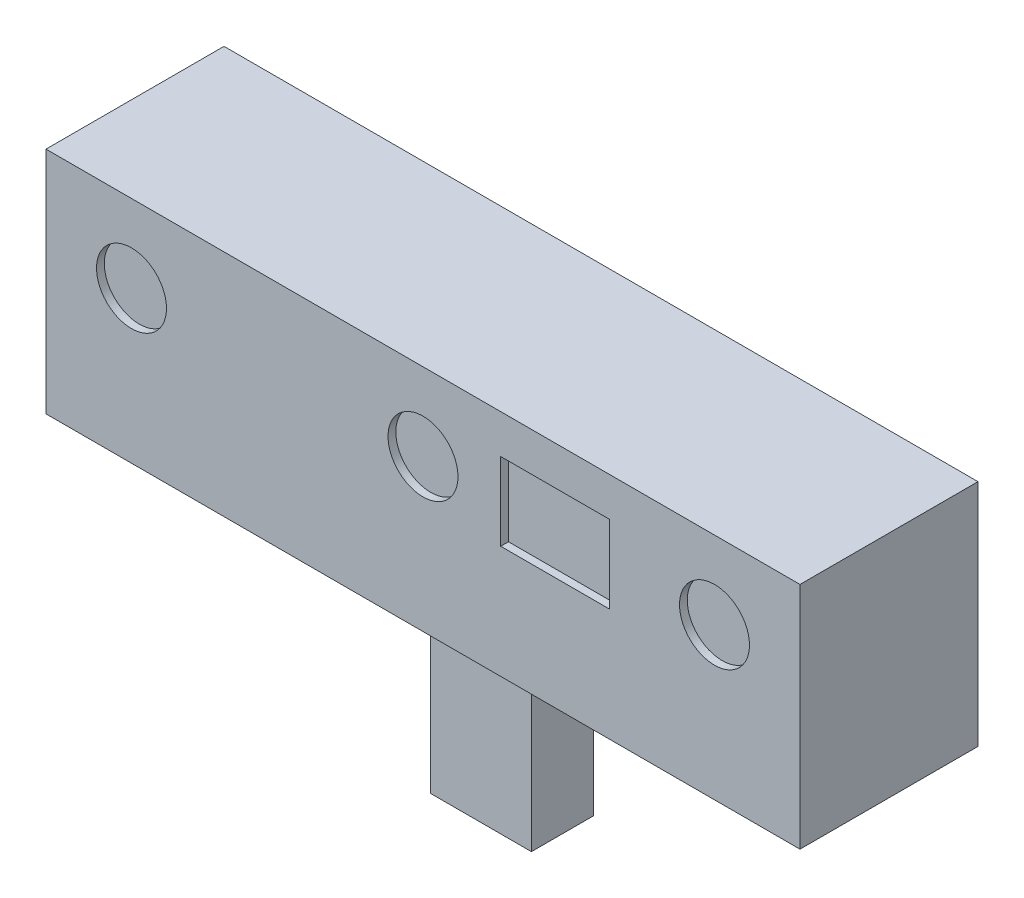
SolidWorks part; units mm, degrees
ref_plane "Front Plane" through (0, 0, 0) normal (0, 0, 1) x (1, 0, 0)
ref_plane "Top Plane" through (0, 0, 0) normal (0, 1, 0) x (1, 0, 0)
ref_plane "Right Plane" through (0, 0, 0) normal (1, 0, 0) x (0, 0, -1)
sketch "SK_Body" plane through (0, 0, 0) normal (0, 0, 1) x (1, 0, 0)
  line L1 (-48.5, -19.5) -> (48.5, -19.5)
  line L2 (-48.5, -19.5) -> (-48.5, 10)
  line L3 (-48.5, 10) -> (48.5, 10)
  line L4 (48.5, -19.5) -> (48.5, 10)
  dimension "D1" = 97
  dimension "D2" = 29.5
  dimension "D3" = 48.5
  dimension "D4" = 19.5
extrude "EX_Body" add sketch "SK_Body" along normal blind 22.9
sketch "SK_VESA_2xM4" plane through (0, 0, 0) normal (0, 0, 1) x (1, 0, 0)
  circle A0 centre (37.5, -4.75) radius 1.65
  circle A1 centre (-37.5, -4.75) radius 1.65
  dimension "D3" = 3.3
  dimension "D6" = 3.3
  dimension "D1" = 37.5
  dimension "D2" = 4.75
  dimension "D4" = 37.5
  dimension "D5" = 4.75
extrude "CUT_VESA_2xM4" cut sketch "SK_VESA_2xM4" along normal blind 8
ref_plane "PL_Xp22_9" through (0, 0, 22.9) normal (0, 0, 1) x (1, 0, 0)
sketch "SK_Lenses" plane through (0, 0, 22.9) normal (0, 0, 1) x (1, 0, 0)
  line L1 (10, -5) -> (24, -5)
  line L2 (10, -5) -> (10, 5)
  line L3 (10, 5) -> (24, 5)
  line L4 (24, -5) -> (24, 5)
  circle A0 centre (37.5, 0) radius 4.5
  circle A1 centre (-37.5, 0) radius 4.5
  circle A2 centre (0, 0) radius 4.5
  dimension "D2" = 9
  dimension "D4" = 9
  dimension "D5" = 9
  dimension "D1" = 37.5
  dimension "D3" = 37.5
  dimension "D6" = 14
  dimension "D7" = 10
  dimension "D8" = 10
  dimension "D9" = 5
extrude "CUT_Lenses" cut sketch "SK_Lenses" against normal blind 1
ref_plane "PL_Zm19_5" through (0, -19.5, 0) normal (0, 1, 0) x (1, 0, 0)
sketch "SK_KeepOut_USB_C" plane through (0, -19.5, 0) normal (0, 1, 0) x (1, 0, 0)
  line L1 (-6.5, -7.45) -> (6.5, -7.45)
  line L2 (-6.5, -7.45) -> (-6.5, -15.45)
  line L3 (-6.5, -15.45) -> (6.5, -15.45)
  line L4 (6.5, -7.45) -> (6.5, -15.45)
  dimension "D1" = 8
  dimension "D2" = 13
  dimension "D3" = 7.45
  dimension "D4" = 6.5
extrude "EX_KeepOut_USB_C" add sketch "SK_KeepOut_USB_C" against normal blind 25
ref_axis "AX_X" through (0, 0, -1.145) along (0, 0, 1)
ref_axis "AX_Y" through (53.35, 0, 0) along (-1, 0, 0)
ref_axis "AX_Z" through (0, 12.725, 0) along (0, -1, 0)
sketch "SK_F_oak_rgb_lens" plane through (0, 0, 0) normal (0, 1, 0) x (1, 0, 0)
  point P0 (0, -22.9)
  dimension "D1" = 22.9
